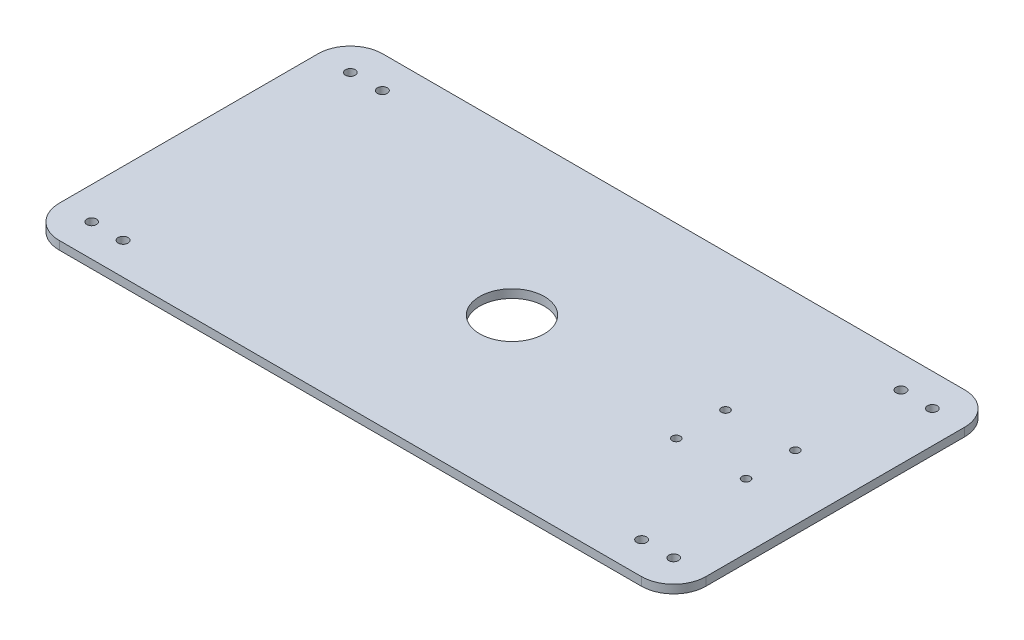
SolidWorks part; units mm, degrees
ref_plane "Front Plane" through (0, 0, 0) normal (0, 0, 1) x (1, 0, 0)
ref_plane "Top Plane" through (0, 0, 0) normal (0, 1, 0) x (1, 0, 0)
ref_plane "Right Plane" through (0, 0, 0) normal (1, 0, 0) x (0, 0, -1)
sketch "Sketch1" plane through (0, 0, 0) normal (0, 1, 0) x (1, 0, 0)
  line L1 (0, 0) -> (200, 0)
  line L2 (0, 0) -> (0, -100)
  line L3 (0, -100) -> (200, -100)
  line L4 (200, 0) -> (200, -100)
  dimension "D1" = 100
  dimension "D2" = 200
extrude "Boss-Extrude1" add sketch "Sketch1" along normal blind 2.6 contours L1 L4 L3 L2
fillet "Fillet1" radius 10 4 edges at (0, 1.3, 0) (0, 1.3, 100) (200, 1.3, 100) (200, 1.3, 0)
sketch "Sketch6" plane through (0, 0, 0) normal (0, -1, 0) x (1, 0, 0)
  line L0 (200, 10) -> (200, 90) construction
  line L1 (10, 0) -> (190, 0) construction
  circle A0 centre (190, 10) radius 1.5
  dimension "D1" = 3
  dimension "D2" = 10
  dimension "D3" = 10
ref_plane "Plane1" through (100, 0, 0) normal (1, 0, 0) x (0, 0, -1)
extrude "Cut-Extrude6" cut sketch "Sketch6" against normal blind 2.6 contours A0
ref_plane "Plane14" through (0, 0, 50) normal (0, 0, 1) x (1, 0, 0)
mirror "Mirror5" about plane through (100, 0, 0) normal (1, 0, 0) of "Cut-Extrude6"
mirror "Mirror6" about plane through (0, 0, 50) normal (0, 0, 1) of "Mirror5"
sketch "Sketch15" plane through (0, 0, 0) normal (0, -1, 0) x (1, 0, 0)
  line L0 (100, 0) -> (100, 100) construction
  line L2 (0, 50) -> (200, 50) construction
  line L4 (0, 10) -> (0, 90) construction
  line L5 (200, 10) -> (200, 90) construction
  line L6 (10, 0) -> (190, 0) construction
  line L7 (10, 100) -> (190, 100) construction
  circle A0 centre (100, 50) radius 10
  dimension "D1" = 20
extrude "Cut-Extrude14" cut sketch "Sketch15" against normal through all contours A0
sketch "Sketch20" plane through (0, 2.6, 0) normal (0, 1, 0) x (1, 0, 0)
  line L0 (-1.43, -50) -> (1.43, -50) construction
  line L1 (158.41, -42.38) -> (158.41, 0) construction
  line L2 (10, 0) -> (190, 0) construction
  line L3 (158.41, 0) -> (158.41, -100) construction
  line L4 (10, -100) -> (190, -100) construction
  line L5 (180, -42.38) -> (180, 0) construction
  line L6 (180, 0) -> (180, -101.354) construction
  line L7 (200, -10) -> (200, -90) construction
  circle A0 centre (158.41, -42.38) radius 1.27
  circle A1 centre (180, -42.38) radius 1.27
  circle A2 centre (158.41, -57.62) radius 1.27
  circle A3 centre (180, -57.62) radius 1.27
  dimension "D1" = 7.62
  dimension "D2" = 7.62
  dimension "D4" = 7.62
  dimension "D7" = 2.54
  dimension "D8" = 2.54
  dimension "D9" = 2.54
  dimension "D10" = 2.54
  dimension "D3" = 21.59
  dimension "D5" = 7.62
  dimension "D6" = 20
extrude "Cut-Extrude15" cut sketch "Sketch20" against normal through all
sketch "Sketch23" plane through (0, 2.6, 0) normal (0, 1, 0) x (1, 0, 0)
  circle A0 centre (19.812, -9.906) radius 1.524
  point P2 (0, 0)
extrude "Cut-Extrude16" cut sketch "Sketch23" against normal blind 2.6
mirror "Mirror7" about plane through (100, 0, 0) normal (1, 0, 0) of "Cut-Extrude16"
mirror "Mirror8" about plane through (0, 0, 50) normal (0, 0, 1) of "Mirror7"
